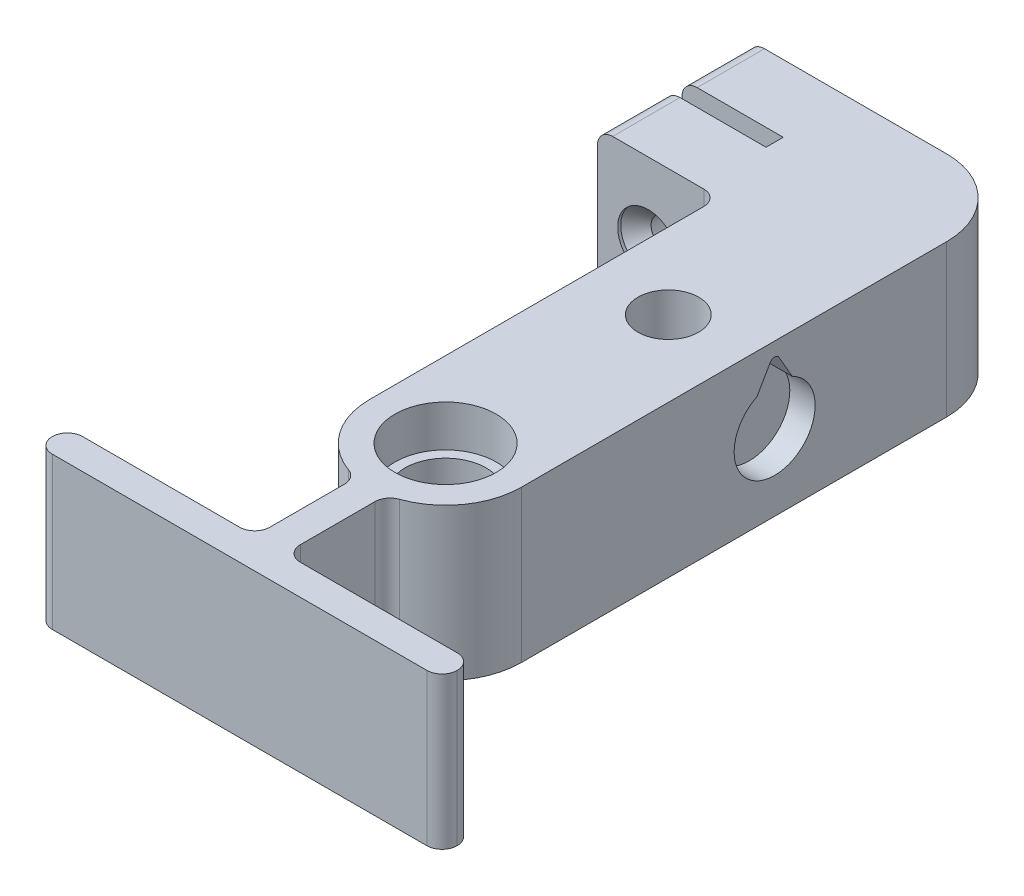
SolidWorks part; units mm, degrees
ref_plane "Front Plane" through (0, 0, 0) normal (0, 0, 1) x (1, 0, 0)
ref_plane "Top Plane" through (0, 0, 0) normal (0, 1, 0) x (1, 0, 0)
ref_plane "Right Plane" through (0, 0, 0) normal (1, 0, 0) x (0, 0, -1)
sketch "Sketch1" plane through (0, 0, 0) normal (0, 1, 0) x (1, 0, 0)
  line L0 (0, 21) -> (0, -21) construction
  line L1 (-7.5, 21) -> (7.5, 21)
  line L2 (-7.5, 21) -> (-7.5, -21)
  line L3 (-7.5, -21) -> (7.5, -21)
  line L4 (7.5, 21) -> (7.5, -21)
  line L5 (-7.5, 21) -> (7.5, -21) construction
  line L6 (-7.5, -21) -> (7.5, 21) construction
  circle A0 centre (0, -13.5) radius 4
  circle A1 centre (0, -13.5) radius 7.5
  point P0 (0, 0)
  dimension "D1" = 8
  dimension "D2" = 15
  dimension "D4" = 42
extrude "Boss-Extrude1" add sketch "Sketch1" along normal mid plane 15 contours L2 | L4 | A1 L4 L1 L2 | A1 A0 | L3 region at (0, 0, -6.6463) region at (0, 0, 6.2121)
sketch "Sketch2" plane through (0, 7.5, 0) normal (0, 1, 0) x (1, 0, 0)
  circle A0 centre (0, -13.5) radius 5
  dimension "D1" = 10
extrude "Cut-Extrude1" cut sketch "Sketch2" against normal blind 4.1
mirror "Mirror1" about plane through (0, 0, 0) normal (0, 1, 0) of "Cut-Extrude1"
sketch "Sketch12" plane through (0, -3.4, 0) normal (0, -1, 0) x (1, 0, 0)
  circle A0 centre (0, 13.5) radius 4 construction
  circle A1 centre (0, 13.5) radius 5
  circle A2 centre (0, 13.5) radius 5
  circle A3 centre (0, 13.5) radius 4
  dimension "D1" = 0
extrude "Cut-Extrude10" cut sketch "Sketch12" against normal blind 1
sketch "Sketch4" plane through (7.5, 0, 0) normal (1, 0, 0) x (0, 0, -1)
  line L0 (-3.1918, 0) -> (3.917, 0) construction
  line L1 (9.75, 3.5969) -> (13.25, 3.5969) construction
  line L2 (-8.5, 7.5) -> (-18.5, 7.5) construction
  line L3 (-8.5, 7.5) -> (-18.5, 7.5)
  line L4 (-13.5, 7.5) -> (-13.5, -7.5) construction
  line L5 (21, -7.5) -> (-13.5, -7.5) construction
  line L6 (11.5, 0) -> (11.5, 7.5) construction
  line L9 (21, 7.5) -> (-13.5, 7.5) construction
  line L10 (11.5, 6.628) -> (9.75, 3.5969)
  line L11 (11.5, 6.628) -> (13.25, 3.5969)
  circle A1 centre (11.5, 0) radius 4
  circle A3 centre (11.5, 5.628) radius 0.5
  dimension "D1" = 25
  dimension "D2" = 8
  dimension "D5" = 1
  dimension "D4" = 3.5
extrude "Cut-Extrude3" cut sketch "Sketch4" against normal blind 2.5 contours A1 | A1 L11 L10 | A3 region at (7.5, 4.5253, -11.5) region at (7.5, 5.628, -11.5) region at (7.5, 0, -11.5)
mirror "Mirror2" about plane through (0, 0, 0) normal (1, 0, 0) of "Cut-Extrude3"
sketch "Sketch18" plane through (0, -7.5, 0) normal (0, -1, 0) x (1, 0, 0)
  line L0 (0, -41.3409) -> (0, 22.3101) construction
  line L4 (7.5, -3.75) -> (-7.5, -3.75) construction
  line L5 (-19.5, -21) -> (-7.5, -21)
  line L6 (7.5, -28.5) -> (7.5, -21)
  line L7 (7.5, -21) -> (7.5, 13.5) construction
  line L8 (-7.5, -21) -> (7.5, -21)
  line L9 (-7.5, -21) -> (-7.5, 13.5) construction
  line L10 (0, -21) -> (0, -36) construction
  line L11 (0, -36) -> (-19.5, -36)
  line L13 (-19.5, -21) -> (-19.5, -36)
  circle A1 centre (0, -28.5) radius 7.5
  line M10 (-7.5, -21) -> (7.5, -21)
  dimension "D1" = 12
extrude "Boss-Extrude3" add sketch "Sketch18" against normal up to surface (15 mm away) contours A1 L6 L8 | A1 M10 | A1 | A1 L13 L11 region at (-12.5923, -7.5, -28.5) region at (5.8247, -7.5, -22.6753) region at (0, -7.5, -28.5) up to face at (0, 7.5, 18.5)
sketch "Sketch7" plane through (0, 7.5, 0) normal (0, 1, 0) x (1, 0, 0)
  line L0 (-19.5, 28.5) -> (7.5, 28.5) construction
  line L8 (7.5, 28.5) -> (7.5, -13.5) construction
  line L9 (-19.5, 27.65) -> (-9.5, 27.65)
  line L10 (-19.5, 27.65) -> (-19.5, 29.35)
  line L11 (-9.5, 27.65) -> (-9.5, 29.35)
  line L12 (-19.5, 29.35) -> (-9.5, 29.35)
  line L13 (-19.5, 27.65) -> (-9.5, 29.35) construction
  line L14 (-9.5, 27.65) -> (-19.5, 29.35) construction
  line L15 (-19.5, 21) -> (-19.5, 36) construction
  point P8 (-14.5, 28.5)
  dimension "D1" = 10
  dimension "D2" = 1.7
extrude "Cut-Extrude7" cut sketch "Sketch7" against normal up to next
sketch "Sketch8" plane through (-40.2452, 0, -36) normal (0, 0, 1) x (1, 0, 0)
  line L5 (20.7452, 0) -> (40.2452, 0) construction
  line L8 (20.7452, 7.5) -> (20.7452, -7.5) construction
  line L9 (40.2452, 7.5) -> (40.2452, -7.5) construction
  circle A2 centre (25.7452, 0) radius 1.5
  dimension "D2" = 5
  dimension "D3" = 3
extrude "Cut-Extrude8" cut sketch "Sketch8" along normal up to surface (15 mm away) contours A2 up to face at (-13.5, 0, -21)
hole_wizard "CSK for M3 Flat Head Machine Screw1" positions "Sketch9" profile "Sketch10" countersink size "M3" standard "ANSI Metric"
sketch "Sketch9" plane through (-83.1458, 0, -21) normal (0, 0, 1) x (1, 0, 0)
  point P6 (68.6458, 0)
  point P17 (0, 0)
  point P18 (0, 0)
  point P19 (0, 0)
  point P20 (0, 0)
sketch "Sketch10" plane through (-14.5, 0, -21) normal (1, 0, 0) x (0, -1, 0)
  line L0 (0, 0) -> (0, 5.9013)
  line L1 (0, 5.9013) -> (1.5, 5)
  line L2 (1.5, 5) -> (1.5, 1.8)
  line L3 (1.5, 1.8) -> (3, 0.3)
  line L4 (3, 0.3) -> (3, 0)
  line L6 (3, 0) -> (0, 0)
  line L7 (-1.5, 1.8) -> (-3, 0.3) construction
  line L10 (0, 5.9013) -> (-1.5, 5) construction
  line L11 (0, -6.35) -> (0, 107.95) construction
  dimension "Hole Dia." = 3
  dimension "Hole Depth" = 5
  dimension "C'Sink Dia." = 6
  dimension "C'Sink Angle" = 90
  dimension "Drill Angle" = 118
  dimension "Head Clearance" = 0.3
sketch "Sketch11" plane through (15, 0, -36) normal (0, 0, 1) x (1, 0, 0)
  line L7 (-34.5, 7.5) -> (-34.5, -7.5) construction
  line L8 (-29.5, -3.4641) -> (-26.5, -1.7321)
  line L15 (-26.5, -1.7321) -> (-26.5, 1.7321)
  line L16 (-26.5, 1.7321) -> (-29.5, 3.4641)
  line L17 (-29.5, 3.4641) -> (-32.5, 1.7321)
  line L18 (-32.5, 1.7321) -> (-32.5, -1.7321)
  line L19 (-32.5, -1.7321) -> (-29.5, -3.4641)
  circle A0 centre (-29.5, 0) radius 3 construction
  dimension "D1" = 6
extrude "Cut-Extrude9" cut sketch "Sketch11" along normal blind 3
sketch "Sketch13" plane through (-44.6536, 0, -29.35) normal (0, 0, 1) x (1, 0, 0)
  line L0 (35.1536, -7.5) -> (35.1536, 7.5) construction
  line L2 (35.1536, -7.5) -> (35.1536, 7.5)
  line L3 (35.1536, 0) -> (44.6536, 0) construction
  line L4 (44.6536, 7.5) -> (44.6536, -7.5) construction
  line L5 (35.1536, 7.5) -> (42.6536, 0)
  line L6 (35.1536, -7.5) -> (42.6536, 0)
  dimension "D1" = 45
extrude "Cut-Extrude11" cut sketch "Sketch13" along normal up to surface (1.7 mm away) contours L5 L6 L2 up to face at (-13, 0, -27.65)
sketch "Sketch16" plane through (0, -7.5, 0) normal (0, -1, 0) x (1, 0, 0)
  line L0 (0, 42.718) -> (0, -5.4521) construction
  line L2 (-1.5, 30.8485) -> (1.5, 30.8485)
  line L3 (-1.5, 30.8485) -> (-1.5, 20.8485)
  line L4 (-1.5, 20.8485) -> (1.5, 20.8485)
  line L5 (1.5, 30.8485) -> (1.5, 20.8485)
  line L6 (-1.5, 30.8485) -> (1.5, 20.8485) construction
  line L7 (-1.5, 20.8485) -> (1.5, 30.8485) construction
  line L8 (-20, 33.8485) -> (20, 33.8485)
  line L9 (-20, 33.8485) -> (-20, 30.8485)
  line L10 (-20, 30.8485) -> (20, 30.8485)
  line L11 (20, 33.8485) -> (20, 30.8485)
  line L12 (-20, 33.8485) -> (20, 30.8485) construction
  line L13 (-20, 30.8485) -> (20, 33.8485) construction
  arc A0 (7.5, 13.5) -> (-7.5, 13.5) centre (0, 13.5) ccw construction
  point P1 (0, 25.8485)
  point P11 (0, 32.3485)
  arc M14 (7.5, 13.5) -> (-7.5, 13.5) centre (0, 13.5) ccw
  dimension "D1" = 3
  dimension "D2" = 10
  dimension "D3" = 40
extrude "Boss-Extrude2" add sketch "Sketch16" against normal up to surface (15 mm away) contours L5 L2 L3 M14 | L11 L8 L9 L10 L2 region at (0, -7.5, 32.3485) region at (0, -7.5, 25.899) up to face at (-8.677, 7.5, -20.323)
fillet "Fillet8" radius 1.5 13 edges at (20, 0, 30.8485) (20, 0, 33.8485) (-20, 0, 33.8485) (-20, 0, 30.8485) (-1.5, 0, 30.8485) (-1.5, 0, 20.8485) (1.5, 0, 20.8485) (1.5, 0, 30.8485) (-19.5, -7.5, -24.325) (-19.5, -7.5, -32.675) (-19.5, 7.5, -32.675) (-19.5, 7.5, -24.325) (-7.5, 0, -21)
sketch "Sketch19" plane through (0, -7.5, 0) normal (0, -1, 0) x (1, 0, 0)
  line L0 (0, 4.3088) -> (0, -5.4508) construction
  circle A0 centre (0, -8.5) radius 3
  circle A2 centre (0, 13.5) radius 5 construction
  dimension "D1" = 6
  dimension "D2" = 22
extrude "Cut-Extrude12" cut sketch "Sketch19" against normal up to next contours A0
